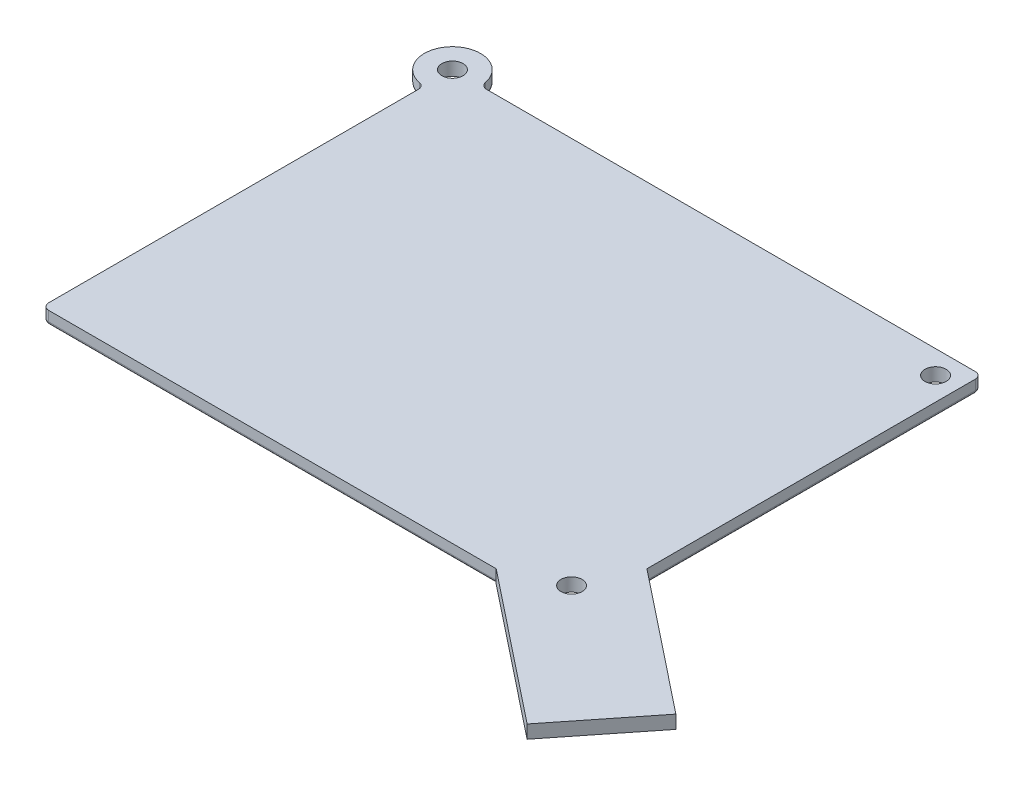
SolidWorks part; units mm, degrees
material "PVC Rigid"
ref_plane "Front Plane" through (0, 0, 0) normal (0, 0, 1) x (1, 0, 0)
ref_plane "Top Plane" through (0, 0, 0) normal (0, 1, 0) x (1, 0, 0)
ref_plane "Right Plane" through (0, 0, 0) normal (1, 0, 0) x (0, 0, -1)
sketch "Sketch1" plane through (0, 0, 0) normal (0, 1, 0) x (1, 0, 0)
  line L1 (-40, -31) -> (40, -31)
  line L2 (-40, -31) -> (-40, 25.8461)
  line L3 (-34.8461, 31) -> (40, 31)
  line L4 (40, -31) -> (40, 31)
  line L5 (-40, -31) -> (40, 31) construction
  line L6 (0, 0) -> (40, -31) construction
  arc A0 (-40, 25.8461) -> (-40.8095, 26.8278) centre (-41, 25.8461) ccw construction
  arc A1 (-35.8278, 31.8095) -> (-34.8461, 31) centre (-34.8461, 32) ccw construction
  arc A2 (-35.8278, 31.8095) -> (-40.8095, 26.8278) centre (-40, 31) ccw construction
  arc A3 (-40, 25.8461) -> (-40.8095, 26.8278) centre (-41, 25.8461) ccw
  arc A4 (-35.8278, 31.8095) -> (-34.8461, 31) centre (-34.8461, 32) ccw
  arc A5 (-35.8278, 31.8095) -> (-40.8095, 26.8278) centre (-40, 31) ccw
  point P0 (0, 0)
  dimension "D1" = 80
  dimension "D2" = 62
extrude "Main Body" add sketch "Sketch1" along normal blind 2
fillet "Corners" radius 1 3 edges at (-40, 1, 31) (40, 1, -31) (40, 1, 31)
fillet "Edge" radius 0.5 10 edges at (-39.7071, 0, 30.7071) (39.7071, 0, -30.7071) (39.7071, 0, 30.7071) (-40, 0, 2.0769) (2.0769, 0, -31) (40, 0, 0) (0, 0, 31) (-40.2285, 0, -26.4823) (-43.0052, 0, -34.0052) (-35.4823, 0, -31.2285)
sketch "Sketch8" plane through (0, 2, 0) normal (0, 1, 0) x (1, 0, 0)
  line L2 (40, -19.6117) -> (61.2107, -36.4473)
  line L3 (40, -30) -> (40, 30) construction
  line L5 (61.2107, -36.4473) -> (51.2636, -48.9794)
  line L6 (51.2636, -48.9794) -> (28.6117, -31)
  line L8 (-39, -31) -> (39, -31) construction
  line L9 (28.6117, -31) -> (40, -19.6117)
  line L10 (39, -30) -> (24.8579, -15.8579) construction
  line L11 (39, -30.5) -> (-39, -30.5) construction
  point P12 (24.4127, -31)
  point P13 (34.3059, -25.3059)
  point P14 (40, -16.911)
  point P15 (28.6117, -31)
  dimension "D1" = 45
  dimension "D2" = 20
  dimension "D3" = 16
  dimension "D4" = 28
extrude "DivingBoard" add sketch "Sketch8" against normal up to surface (2 mm away) up to face at (-7.6864, 0, -5.8864)
sketch "Sketch7" plane through (0, 0, 0) normal (0, -1, 0) x (-1, 0, 0)
  line L0 (39, -31) -> (-28.6117, -31) construction
  line L3 (-40, -19.6117) -> (-40, 30) construction
  line L4 (-39, 31) -> (34.8461, 31) construction
  circle A0 centre (40, 31) radius 1.6
  arc A1 (40.7143, 27.3187) -> (36.3187, 31.7143) centre (40, 31) ccw construction
  circle A2 centre (-36.5, -27.5) radius 1.6
  circle A3 centre (-36.5, 27.5) radius 1.6
  dimension "D1" = 3.2
  dimension "D4" = 3.2
  dimension "D5" = 3.2
  dimension "D2" = 3.5
  dimension "D3" = 3.5
  dimension "D6" = 3.5
extrude "Lid Holes" cut sketch "Sketch7" against normal through all both and the other way through all
sketch "Sketch4" plane through (0, 0, 0) normal (0, -1, 0) x (-1, 0, 0)
  circle A0 centre (-30.0048, 23.7064) radius 2.325
  circle A1 centre (-30.0048, 15.7064) radius 2.325
  point P2 (0, 0)
  dimension "D1" = 4.65
  dimension "D2" = 4.65
  dimension "D3" = 8
extrude "Boss-Extrude3" add sketch "Sketch4" along normal blind 1.6
fillet "Fillet3" radius 0.05 1 edges at (30.0048, -1.6, -26.0314)
pattern_linear "LPattern5" count 4 spacing 8 along (-1, 0, 0) of "Boss-Extrude3", "Fillet3"
equation "\"D3@Sketch7\"=\"D2@Sketch7\""
equation "\"D4@Sketch7\"=\"D1@Sketch7\""
equation "\"D5@Sketch7\"=\"D1@Sketch7\""
equation "\"D2@Sketch4\"=\"D1@Sketch4\""
